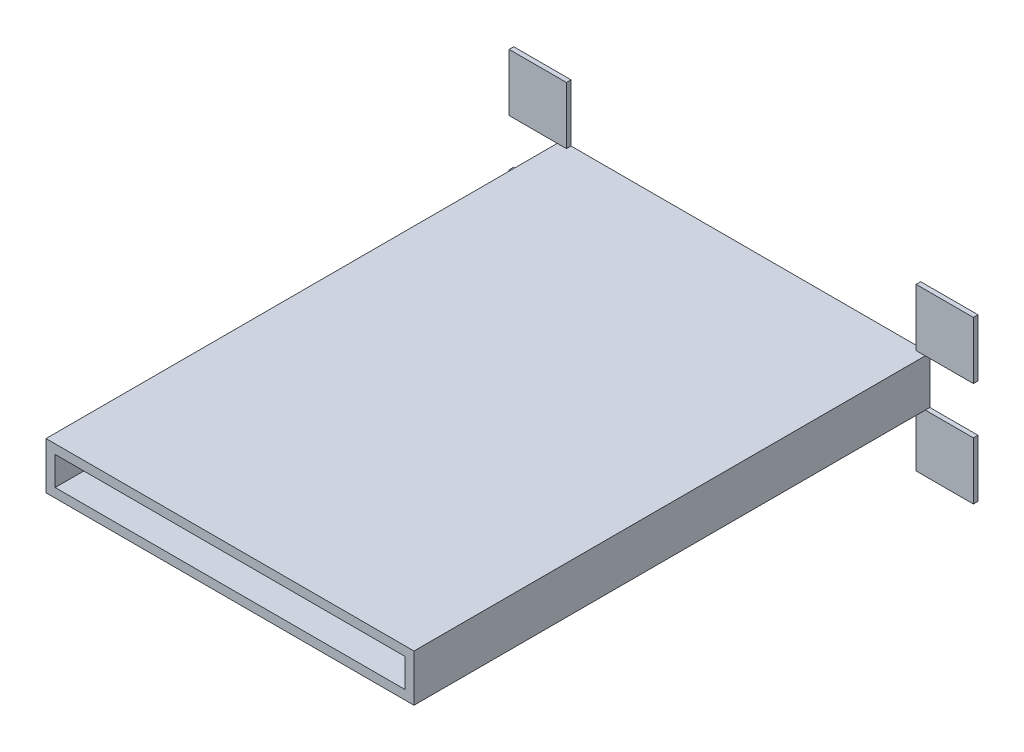
SolidWorks part; units mm, degrees
ref_plane "Front Plane" through (0, 0, 0) normal (0, 0, 1) x (1, 0, 0)
ref_plane "Top Plane" through (0, 0, 0) normal (0, 1, 0) x (1, 0, 0)
ref_plane "Right Plane" through (0, 0, 0) normal (1, 0, 0) x (0, 0, -1)
sketch "Sketch1" plane through (0, 0, 0) normal (0, 0, 1) x (1, 0, 0)
  line L0 (-32.1, -4.1) -> (-32.1, 4.1)
  line L1 (-30.5, -2.5) -> (30.5, -2.5)
  line L2 (-30.5, -2.5) -> (-30.5, 2.5)
  line L3 (-30.5, 2.5) -> (30.5, 2.5)
  line L4 (30.5, -2.5) -> (30.5, 2.5)
  line L5 (0, 2.5) -> (0, -2.5) construction
  line L6 (-30.5, 0) -> (30.5, 0) construction
  line L7 (-32.1, 4.1) -> (32.1, 4.1)
  line L8 (32.1, -4.1) -> (32.1, 4.1)
  line L9 (-32.1, -4.1) -> (32.1, -4.1)
  point P0 (0, 0)
  point P8 (0, 0)
  point P9 (0, 0)
  dimension "D1" = 61
  dimension "D2" = 5
  dimension "D3" = 1.6
extrude "Boss-Extrude1" add sketch "Sketch1" along normal blind 90
sketch "Sketch2" plane through (0, 0, 0) normal (0, 0, -1) x (-1, 0, 0)
  line L0 (32.1, 4.1) -> (-32.1, 4.1) construction
  line L1 (-2, -4.1) -> (2, -4.1)
  line L2 (-2, -4.1) -> (-2, 4.1)
  line L3 (-2, 4.1) -> (2, 4.1)
  line L4 (2, -4.1) -> (2, 4.1)
  line L5 (0, 4.1) -> (0, -4.1) construction
  line L6 (-2, 0) -> (2, 0) construction
  point P0 (0, 0)
  dimension "D1" = 4
extrude "Boss-Extrude2" add sketch "Sketch2" against normal blind 2
sketch "Sketch4" plane through (0, -4.1, 0) normal (0, -1, 0) x (1, 0, 0)
  line L0 (-8.6, 26.6) -> (-7, 26.6) construction
  line L1 (-7, 52.6) -> (7, 52.6) construction
  line L2 (-7, 52.6) -> (-7, 26.6)
  line L3 (-7, 26.6) -> (7, 26.6)
  line L4 (7, 52.6) -> (7, 26.6)
  line L5 (0, 26.6) -> (0, 52.6) construction
  line L6 (-7, 39.6) -> (7, 39.6) construction
  line L7 (-8.6, 52.6) -> (8.6, 52.6) construction
  line L8 (-8.6, 52.6) -> (-8.6, 25)
  line L9 (-8.6, 25) -> (8.6, 25)
  line L10 (8.6, 52.6) -> (8.6, 25)
  line L11 (0, 25) -> (0, 52.6) construction
  line L12 (-8.6, 38.8) -> (8.6, 38.8) construction
  line L13 (-7, 26.6) -> (-7, 25) construction
  line L14 (-7, 52.6) -> (-8.6, 52.6)
  line L15 (7, 52.6) -> (8.6, 52.6)
  line L16 (-32.1, 0) -> (32.1, 0) construction
  point P0 (0, 39.6)
  point P4 (0, 38.8)
  point P8 (7.4008, 3.0865)
  dimension "D1" = 1.6
  dimension "D2" = 26
  dimension "D3" = 14
  dimension "D4" = 25
extrude "Boss-Extrude4" add sketch "Sketch4" along normal blind 8
sketch "Sketch5" plane through (0, -12.1, 0) normal (0, -1, 0) x (1, 0, 0)
  line L1 (-8.6, 52.6) -> (8.6, 52.6)
  line L2 (-8.6, 52.6) -> (-8.6, 25)
  line L3 (-8.6, 25) -> (8.6, 25)
  line L4 (8.6, 52.6) -> (8.6, 25)
  line L5 (0, 25) -> (0, 52.6) construction
  line L6 (-8.6, 38.8) -> (8.6, 38.8) construction
  point P108 (0, 38.8)
extrude "Boss-Extrude5" add sketch "Sketch5" along normal blind 1.6
chamfer "Chamfer3" distance 11 angle 45 1 edges at (0, -4.1, 25)
fillet "Fillet1" radius 3 2 edges at (8.6, -4.1, 33.3) (-8.6, -4.1, 33.3)
fillet "Fillet2" radius 2 4 edges at (-2, -2.5, 1) (-2, 2.5, 1) (2, 2.5, 1) (2, -2.5, 1)
fillet "Fillet3" radius 3 2 edges at (-9.3, -4.1, 52.6) (9.3, -4.1, 52.6)
sketch "Sketch6" [suppressed] plane through (0, 4.1, 0) normal (0, 1, 0) x (1, 0, 0)
  line L0 (0, -1053.2004) -> (0, 48946.7996) construction
  line L1 (31.6, -90) -> (-31.6, -90) construction
  line L2 (22.4, -40) -> (20, -40)
  line L3 (22.4, -40) -> (22.4, -90)
  line L4 (22.4, -90) -> (20, -90)
  line L5 (20, -40) -> (20, -90)
  line L6 (21.2, -90) -> (21.2, -40) construction
  line L7 (22.4, -65) -> (20, -65) construction
  line L8 (-22.4, -90) -> (-20, -90)
  line L9 (-20, -40) -> (-20, -90)
  line L10 (-22.4, -40) -> (-20, -40)
  line L11 (-22.4, -40) -> (-22.4, -90)
  point P1 (21.2, -65)
  dimension "D1" = 50
  dimension "D2" = 2.4
  dimension "D3" = 40
extrude "Boss-Extrude6" [suppressed] add sketch "Sketch6" along normal blind 15
sketch "Sketch7" [suppressed] plane through (22.4, 0, 0) normal (1, 0, 0) x (0, 0, -1)
  line L0 (-40, 4.1) -> (-55, 19.1)
  line L1 (-90, 19.1) -> (-40, 19.1) construction
  line L2 (-55, 19.1) -> (-40, 19.1)
  line L3 (-40, 19.1) -> (-40, 4.1)
extrude "Cut-Extrude1" [suppressed] cut sketch "Sketch7" against normal through all
fillet "Fillet4" [suppressed] radius 10
fillet "Fillet5" [suppressed] radius 4
fillet "Fillet6" [suppressed] radius 6
sketch "Sketch8" [suppressed] plane through (0, 0, 90) normal (0, 0, 1) x (1, 0, 0)
  line L0 (-32.1, 4.1) -> (32.1, 4.1) construction
  line L1 (-32.1, 5.1) -> (-32.1, 4.1)
  line L2 (-32.1, 4.1) -> (32.1, 4.1)
  line L3 (32.1, 4.1) -> (32.1, 5.1)
  arc A0 (-32.1, 5.1) -> (32.1, 5.1) centre (0, 519.805) ccw
  point P5 (0, 0)
  point P8 (0, 0)
  point P11 (0, 0)
  point P12 (-30.9776, 6.9946)
  point P13 (0, 0)
  point P14 (-31.1076, 8.6767)
  line M3 (32.1, 4.1) -> (-32.1, 4.1)
  dimension "D1" = 1
extrude "Boss-Extrude7" [suppressed] add sketch "Sketch8" against normal offset from surface (80 mm away) 10 contours A0 L3 M3 | A0 L1 L2
chamfer "Chamfer1" [suppressed] distance 1 angle 45
chamfer "Chamfer2" [suppressed] distance 0.8 angle 45
sketch "Sketch3" plane through (0, 0, 0) normal (0, 0, -1) x (-1, 0, 0)
  line L0 (-30.5, 4.1) -> (-32.1, 4.1) construction
  line L1 (-40.5, 14.1) -> (-30.5, 14.1)
  line L2 (-40.5, 14.1) -> (-40.5, 4.1)
  line L3 (-40.5, 4.1) -> (-30.5, 4.1)
  line L4 (-30.5, 14.1) -> (-30.5, 4.1)
  line L5 (-35.5, 4.1) -> (-35.5, 14.1) construction
  line L6 (-40.5, 9.1) -> (-30.5, 9.1) construction
  line L7 (32.1, 4.1) -> (-32.1, 4.1) construction
  line L10 (30.5, 0) -> (-30.5, 0) construction
  line L11 (0, 2.5) -> (0, -2.5) construction
  line L12 (30.5, 0) -> (-30.5, 0) construction
  line L13 (0, 2.5) -> (0, -2.5) construction
  line L14 (40.5, 4.1) -> (30.5, 4.1)
  line L15 (30.5, 14.1) -> (30.5, 4.1)
  line L16 (40.5, 14.1) -> (30.5, 14.1)
  line L17 (40.5, 14.1) -> (40.5, 4.1)
  line L18 (40.5, -14.1) -> (40.5, -4.1)
  line L19 (40.5, -14.1) -> (30.5, -14.1)
  line L20 (30.5, -14.1) -> (30.5, -4.1)
  line L21 (40.5, -4.1) -> (30.5, -4.1)
  line L22 (-40.5, -4.1) -> (-30.5, -4.1)
  line L23 (-30.5, -14.1) -> (-30.5, -4.1)
  line L24 (-40.5, -14.1) -> (-30.5, -14.1)
  line L25 (-40.5, -14.1) -> (-40.5, -4.1)
  point P0 (-35.5, 9.1)
  dimension "D1" = 1.6
  dimension "D2" = 10
extrude "Boss-Extrude3" add sketch "Sketch3" against normal blind 0.8
